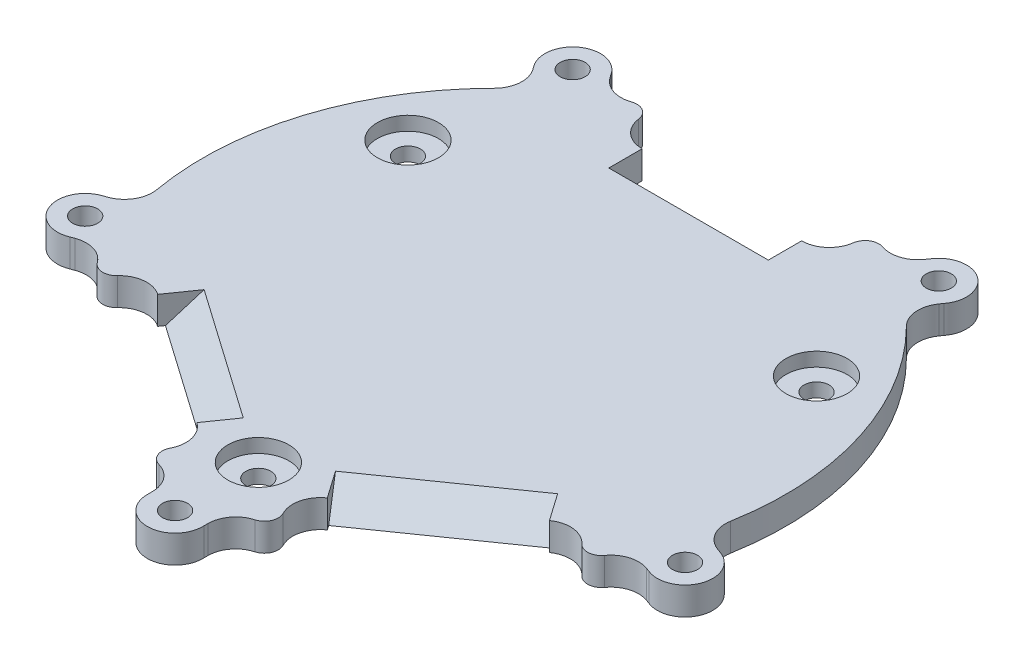
SolidWorks part; units mm, degrees
ref_plane "Plan de face" through (0, 0, 0) normal (0, 0, 1) x (1, 0, 0)
ref_plane "Plan de dessus" through (0, 0, 0) normal (0, 1, 0) x (1, 0, 0)
ref_plane "Plan de droite" through (0, 0, 0) normal (1, 0, 0) x (0, 0, -1)
sketch "Sketch1" plane through (0, 0, 0) normal (0, 1, 0) x (1, 0, 0)
  line L0 (0, 0) -> (0, 41) construction
  line L1 (0, 0) -> (-23.5166, -33.5852) construction
  line L2 (0, 0) -> (23.5166, -33.5852) construction
  line L3 (-39.3263, -22.5152) -> (-7.707, -44.6553)
  line L4 (7.707, -44.6553) -> (39.3263, -22.5152)
  line L5 (-19.3, 41) -> (19.3, 41)
  line L6 (-19.3, 41) -> (-19.3, 48.8238)
  line L8 (19.3, 41) -> (19.3, 48.8238)
  line L9 (7.707, -44.6553) -> (12.1945, -51.0641)
  line L11 (39.3263, -22.5152) -> (43.8138, -28.9241)
  line L12 (-7.707, -44.6553) -> (-12.1945, -51.0641)
  line L13 (-39.3263, -22.5152) -> (-43.8138, -28.9241)
  line L14 (0, 0) -> (0, -42.5) construction
  line L15 (0, 0) -> (-36.8061, 21.25) construction
  line L16 (0, 0) -> (36.8061, 21.25) construction
  arc A0 (-19.3, 48.8238) -> (-43.8138, -28.9241) centre (0, 0) ccw
  arc A1 (43.8138, -28.9241) -> (19.3, 48.8238) centre (0, 0) ccw
  circle A3 centre (-36.8061, 21.25) radius 2.25 construction
  circle A4 centre (36.8061, 21.25) radius 2.25 construction
  circle A6 centre (0, -42.5) radius 2.25 construction
  arc A7 (-12.1945, -51.0641) -> (12.1945, -51.0641) centre (0, 0) ccw
  circle A8 centre (-36.8061, 21.25) radius 5.5
  circle A9 centre (36.8061, 21.25) radius 5.5
  circle A10 centre (0, -42.5) radius 5.5
  point P25 (23.5166, -33.5852)
  point P26 (-23.5166, -33.5852)
  dimension "D1" = 105
  dimension "D5" = 35
  dimension "D6" = 38.6
  dimension "D10" = 4.5
  dimension "D4" = 11
  dimension "D9" = 42.5
  dimension "D2" = 35
  dimension "D3" = 41
  dimension "D7" = 120
  dimension "D8" = 120
extrude "Boss-Extrude1" add sketch "Sketch1" along normal blind 5 contours L4 A0 L5 L3 | A8 | A9 | A10 region at (0, 0, -1.6314) region at (-36.8061, 0, -21.25) region at (36.8061, 0, -21.25) region at (0, 0, 42.5)
extrude "Enlèv. mat.-Extru.3" cut sketch "Sketch1<3>" against normal blind 2.5 from surface contours A8 | A9 | A10 region at (-36.8061, 0, -21.25) region at (36.8061, 0, -21.25) region at (0, 0, 42.5) starting at face at (0, 5, 8.7026)
sketch "Sketch1<3>" plane through (0, 0, 0) normal (0, 1, 0) x (1, 0, 0) same geometry as "Sketch1"
sketch "Esquisse4" plane through (0, 5, 0) normal (0, 1, 0) x (1, 0, 0)
  point P0 (0, -42.5)
  point P3 (36.8061, 21.25)
  point P6 (-36.8061, 21.25)
hole_wizard "M4 Clearance Hole1" positions "Esquisse4" profile "Esquisse3" hole size "M4" standard "ANSI Metric" end condition up to next
sketch "Esquisse3" plane through (0, 5, 42.5) normal (1, 0, 0) x (0, 0, 1)
  line L0 (0, 0) -> (0, 5)
  line L1 (0, 5) -> (2.25, 5)
  line L2 (2.25, 5) -> (2.25, 0)
  line L5 (2.25, 0) -> (0, 0)
  line L11 (0, -6.35) -> (0, 107.95) construction
  dimension "Thru Hole Dia." = 4.5
  dimension "Thru Hole Depth" = 5
fillet "Congé1" radius 2.5 6 edges at (19.3, 2.5, -48.8238) (-19.3, 2.5, -48.8238) (-43.8138, 2.5, 28.9241) (43.8138, 2.5, 28.9241) (12.1945, 2.5, 51.0641) (-12.1945, 2.5, 51.0641)
sketch "Esquisse5" plane through (0, 5, 0) normal (0, 1, 0) x (1, 0, 0)
  line L0 (0, 0) -> (0, -57.5) construction
  line L1 (0, 0) -> (54.0323, -19.6662) construction
  line L2 (0, 0) -> (32.9806, 47.1012) construction
  line L3 (0, 0) -> (-32.9806, 47.1012) construction
  line L4 (0, 0) -> (-54.0323, -19.6662) construction
  line L5 (-52.1196, -24.2858) -> (-47.4016, -22.5686)
  line L6 (-55.5365, -14.8978) -> (-50.8185, -13.1806)
  line L7 (-36.9478, 44.058) -> (-34.068, 39.9452)
  line L8 (-28.7641, 49.7883) -> (-25.8843, 45.6755)
  line L9 (36.9478, 44.058) -> (34.068, 39.9452)
  line L10 (28.7641, 49.7883) -> (25.8843, 45.6755)
  line L11 (52.1196, -24.2858) -> (47.4016, -22.5686)
  line L12 (55.5365, -14.8978) -> (50.8185, -13.1806)
  line L13 (4.9953, -57.2826) -> (4.9953, -52.2618)
  line L14 (-4.9953, -57.2826) -> (-4.9953, -52.2618)
  arc A0 (-4.9953, -57.2826) -> (-52.1196, -24.2858) centre (0, 0) ccw construction
  arc A1 (52.1196, -24.2858) -> (55.5365, -14.8978) centre (54.0323, -19.6662) ccw
  arc A2 (-4.9953, -57.2826) -> (4.9953, -57.2826) centre (0, -57.5) ccw
  arc A3 (-55.5365, -14.8978) -> (-52.1196, -24.2858) centre (-54.0323, -19.6662) ccw
  arc A4 (-28.7641, 49.7883) -> (-36.9478, 44.058) centre (-32.9806, 47.1012) ccw
  arc A5 (36.9478, 44.058) -> (28.7641, 49.7883) centre (32.9806, 47.1012) ccw
  arc A6 (-8.3495, -51.8318) -> (8.3495, -51.8318) centre (0, 0) ccw construction
  arc A7 (-22.89, 47.2472) -> (-45.8503, -25.5735) centre (0, 0) ccw construction
  arc A8 (45.8503, -25.5735) -> (22.89, 47.2472) centre (0, 0) ccw construction
  arc A9 (-8.3495, -51.8318) -> (8.3495, -51.8318) centre (0, 0) ccw construction
  arc A10 (47.4016, -22.5686) -> (50.8185, -13.1806) centre (0, 0) ccw
  arc A11 (34.068, 39.9452) -> (25.8843, 45.6755) centre (0, 0) ccw
  arc A12 (-25.8843, 45.6755) -> (-34.068, 39.9452) centre (0, 0) ccw
  arc A13 (-50.8185, -13.1806) -> (-47.4016, -22.5686) centre (0, 0) ccw
  arc A14 (-4.9953, -52.2618) -> (4.9953, -52.2618) centre (0, 0) ccw
  dimension "D1" = 70
  dimension "D5" = 10
  dimension "D2" = 70
  dimension "D3" = 75
  dimension "D4" = 75
extrude "Boss.-Extru.1" add sketch "Esquisse5" against normal up to surface (5 mm away) up to face at (0, 0, 44.75)
sketch "Esquisse8" plane through (0, 5, 0) normal (0, 1, 0) x (1, 0, 0)
  point P0 (0, -57.5)
  point P3 (54.0323, -19.6662)
  point P6 (32.9806, 47.1012)
  point P9 (-32.9806, 47.1012)
  point P12 (-54.0323, -19.6662)
hole_wizard "M4 Clearance Hole2" positions "Esquisse8" profile "Esquisse7" hole size "M4" standard "ANSI Metric" end condition up to next
sketch "Esquisse7" plane through (0, 5, 57.5) normal (1, 0, 0) x (0, 0, 1)
  line L0 (0, 0) -> (0, 5)
  line L1 (0, 5) -> (2.25, 5)
  line L2 (2.25, 5) -> (2.25, 0)
  line L5 (2.25, 0) -> (0, 0)
  line L11 (0, -6.35) -> (0, 107.95) construction
  dimension "Thru Hole Dia." = 4.5
  dimension "Thru Hole Depth" = 5
fillet "Congé2" radius 5 16 edges at (47.4016, 2.5, 22.5686) (50.8185, 2.5, 13.1806) (34.068, 2.5, -39.9452) (-34.068, 2.5, -39.9452) (-50.8185, 2.5, 13.1806) (-47.4016, 2.5, 22.5686) (4.9953, 2.5, 52.2618) (-4.9953, 2.5, 52.2618) (25.8843, 2.5, -45.6755) (-25.8843, 2.5, -45.6755) (-7.707, 2.5, 44.6553) (-39.3263, 2.5, 22.5152) (-19.3, 2.5, -41) (19.3, 2.5, -41) (39.3263, 2.5, 22.5152) (7.707, 2.5, 44.6553)
ref_plane "Plan1" through (11.769, 0, 8.2408) normal (0.8192, 0, 0.5736) x (0, 1, 0)
sketch "Esquisse9" plane through (11.769, 0, 8.2408) normal (0.8192, 0, 0.5736) x (0, 1, 0)
  line L4 (5, 44.8512) -> (5, 49.3512) construction
  line L8 (0, 41) -> (5, 41) construction
  line L9 (0, 41) -> (5, 41)
  line L10 (5, 41) -> (5, 35)
  line L11 (5, 35) -> (0, 40)
  line L12 (0, 40) -> (0, 41)
  line L13 (0, 49.3512) -> (0, 44.8512) construction
  dimension "D1" = 1
  dimension "D2" = 45
extrude "Enlèv. mat.-Extru.4" cut sketch "Esquisse9" against normal up to vertex (28.7346 mm away) up to point (-35.2857, 5, 25.3445)
ref_plane "Plan2" through (-11.769, 0, 8.2408) normal (-0.8192, 0, 0.5736) x (0, -1, 0)
sketch "Esquisse10" plane through (-11.769, 0, 8.2408) normal (-0.8192, 0, 0.5736) x (0, -1, 0)
  line L0 (-5, 41) -> (-5, 35)
  line L1 (-5, 35) -> (0, 40)
  line L2 (0, 40) -> (0, 41)
  line L3 (0, 41) -> (-5, 41)
  line L4 (-5, -1.5302) -> (-5, 0.522) construction
  line L5 (-5, 41) -> (0, 41) construction
  line L6 (0, 44.8512) -> (0, 49.3512) construction
  dimension "D1" = 1
  dimension "D2" = 45
extrude "Enlèv. mat.-Extru.5" cut sketch "Esquisse10" against normal up to vertex (28.7346 mm away) up to point (35.2857, 5, 25.3445)
ref_plane "Plan3" through (-14.3673, 0, 0) normal (-1, 0, 0) x (0, 1, 0)
sketch "Esquisse11" plane through (-14.3673, 0, 0) normal (-1, 0, 0) x (0, 1, 0)
  line L0 (0, 41) -> (5, 41)
  line L1 (5, 41) -> (5, 35)
  line L2 (5, 35) -> (0, 40)
  line L3 (0, 40) -> (0, 41)
  line L5 (5, -59.75) -> (5, -55.25) construction
  line L6 (0, 23.5) -> (0, 19) construction
  line L8 (0, 41) -> (5, 41) construction
  dimension "D1" = 1
  dimension "D2" = 45
extrude "Enlèv. mat.-Extru.6" cut sketch "Esquisse11" against normal up to vertex (28.7346 mm away) up to point (14.3673, 5, -41)
